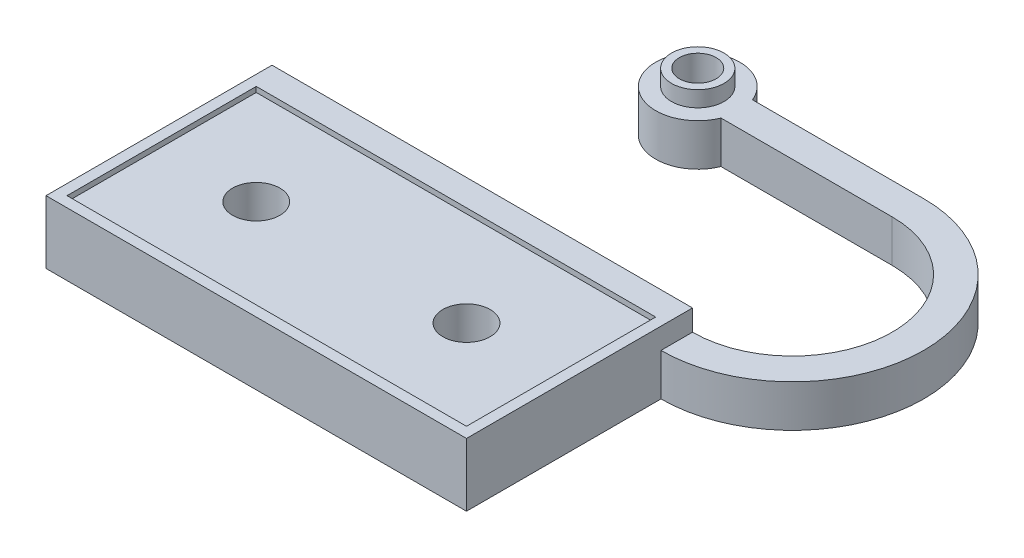
SolidWorks part; units mm, degrees
ref_plane "Front Plane" through (0, 0, 0) normal (0, 0, 1) x (1, 0, 0)
ref_plane "Top Plane" through (0, 0, 0) normal (0, 1, 0) x (1, 0, 0)
ref_plane "Right Plane" through (0, 0, 0) normal (1, 0, 0) x (0, 0, -1)
sketch "Sketch1" plane through (0, 0, 0) normal (0, 1, 0) x (1, 0, 0)
  line L1 (-20, 10) -> (20, 10)
  line L2 (-20, 10) -> (-20, -10)
  line L3 (-20, -10) -> (20, -10)
  line L4 (20, 10) -> (20, -10)
  line L5 (0, -10) -> (0, 10) construction
  line L6 (-20, 0) -> (20, 0) construction
  line L7 (-20, 11.5) -> (20, 11.5) construction
  line L8 (-20, 11.5) -> (-20, 8.5) construction
  line L9 (-20, 8.5) -> (20, 8.5) construction
  line L10 (20, 11.5) -> (20, 8.5) construction
  line L11 (0, 8.5) -> (0, 11.5) construction
  line L12 (-20, 10) -> (20, 10) construction
  line L16 (-20, 33.5) -> (0, 33.5) construction
  line L17 (-20, 33.5) -> (-20, 30.5) construction
  line L18 (-20, 30.5) -> (0, 30.5) construction
  line L19 (0, 33.5) -> (0, 30.5) construction
  line L20 (-10, 30.5) -> (-10, 33.5) construction
  line L21 (-20, 32) -> (0, 32) construction
  line L23 (20, 30.5) -> (3.7081, 30.5)
  line L24 (-20, 11.5) -> (20, 11.5)
  line L25 (-20, 11.5) -> (-20, 8.5)
  line L26 (-20, 8.5) -> (20, 8.5)
  line L27 (20, 11.5) -> (20, 8.5)
  line L28 (0, 8.5) -> (0, 11.5) construction
  line L29 (-20, 10) -> (20, 10) construction
  line L30 (-20, 11.5) -> (20, 11.5)
  line L31 (-20, 8.5) -> (-20, 11.5)
  line L32 (20, 8.5) -> (-20, 8.5)
  line L33 (3.7081, 33.5) -> (20, 33.5)
  circle A0 centre (-10, 0) radius 2.25
  circle A1 centre (10, 0) radius 2.25
  arc A2 (-20, 10) -> (-20, 32) centre (-20, 21) cw construction
  arc A3 (-20, 33.5) -> (-20, 8.5) centre (-20, 21) ccw construction
  arc A4 (-20, 30.5) -> (-20, 11.5) centre (-20, 21) ccw construction
  arc A5 (-20, 30.5) -> (-20, 33.5) centre (-20, 32) ccw construction
  arc A6 (-20, 8.5) -> (-20, 11.5) centre (-20, 10) ccw construction
  circle A10 centre (0, 32) radius 1.75
  circle A11 centre (0, 32) radius 4 construction
  arc A13 (3.7081, 30.5) -> (3.7081, 33.5) centre (0, 32) cw
  arc A14 (20, 11.5) -> (20, 30.5) centre (20, 21) ccw
  arc A15 (20, 33.5) -> (20, 8.5) centre (20, 21) cw
  point P0 (0, 0)
  point P10 (-31, 21)
  point P460 (-10, 32)
  dimension "D4" = 4.5
  dimension "D5" = 1.5
  dimension "D7" = 8
  dimension "D8" = 3.5
  dimension "D1" = 20
  dimension "D2" = 40
  dimension "D3" = 10
  dimension "D6" = 11
extrude "Boss-Extrude3" add sketch "Sketch1" along normal blind 6 contours L2 L3 L4 A0 A1 | L25 L1 | L2 L1 region at (0, 0, -10.75) region at (0, 0, -9.25) region at (0, 0, 0.7837)
extrude "Boss-Extrude4" add sketch "Sketch1<5>" along normal blind 4 contours L2 L25 A10 region at (20.457, 0, -10.75)
sketch "Sketch1<5>" plane through (0, 0, 0) normal (0, 1, 0) x (1, 0, 0) same geometry as "Sketch1"
sketch "Sketch2" plane through (0, 4, 0) normal (0, 1, 0) x (1, 0, 0)
  circle A0 centre (0, 32) radius 1.75
  circle A1 centre (0, 32) radius 2.5
  dimension "D1" = 5
  dimension "D2" = 3.5
extrude "Boss-Extrude5" add sketch "Sketch2" along normal blind 1.5
sketch "Sketch3" plane through (0, 6, 0) normal (0, 1, 0) x (1, 0, 0)
  line L0 (-19, 9) -> (19, 9)
  line L1 (-18, 8) -> (18, 8)
  line L2 (-18, 8) -> (-18, -8)
  line L3 (-18, -8) -> (18, -8)
  line L4 (18, 8) -> (18, -8)
  line L5 (0, -8) -> (0, 8) construction
  line L6 (-18, 0) -> (18, 0) construction
  line L7 (19, 9) -> (19, -9)
  line L8 (-19, -9) -> (19, -9)
  line L9 (-19, 9) -> (-19, -9)
  point P0 (0, 0)
  dimension "D1" = 16
  dimension "D2" = 36
  dimension "D3" = 1
extrude "Cut-Extrude1" cut sketch "Sketch3" against normal blind 0.5 contours L8 L7 L0 L9
